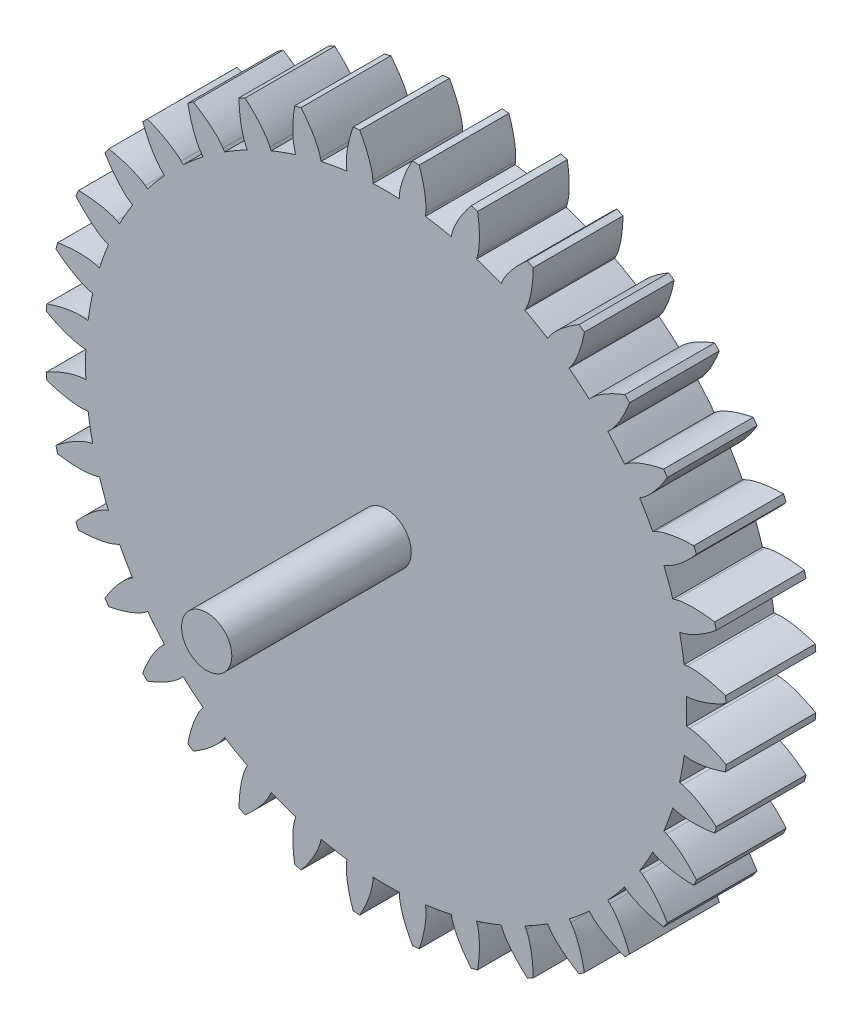
SolidWorks part; units mm, degrees
ref_plane "前视基准面" through (0, 0, 0) normal (0, 0, 1) x (1, 0, 0)
ref_plane "上视基准面" through (0, 0, 0) normal (0, 1, 0) x (1, 0, 0)
ref_plane "右视基准面" through (0, 0, 0) normal (1, 0, 0) x (0, 0, -1)
other "Configuration Table"
sketch "草图1" plane through (0, 0, 0) normal (0, 0, 1) x (1, 0, 0)
  line L0 (0, 0) -> (3, 0) construction
  line L1 (0, 0) -> (2.8978, 0.7765) construction
  line L2 (0, 0) -> (2.7305, 0.701)
  line L3 (2.8978, 0.7765) -> (2.8978, -0.7765) construction
  line L4 (0, 0) -> (2.7305, -0.701)
  circle A0 centre (0, 0) radius 4
  circle A1 centre (0, 0) radius 3 construction
  circle A2 centre (0, 0) radius 1.75
  circle A3 centre (0, 0) radius 2.8191 construction
  circle A4 centre (0, 0) radius 1.4
  spline S0 degree 4 poles (2.7305, 0.701) (2.7514, 0.7063) (2.8083, 0.7255) (2.9105, 0.779) (3.0627, 0.8875) (3.236, 1.0573) (3.4253, 1.3046) (3.6012, 1.6247) (3.742, 2.0003) (3.8364, 2.4221) (3.8779, 2.852) (3.8707, 3.2837) (3.8157, 3.7334) (3.69, 4.2802) (3.4574, 4.9086) (3.0836, 5.5918) (2.5556, 6.2772) (1.9356, 6.8796) (1.2391, 7.3923) (0.4849, 7.8122) (-0.3175, 8.1368) (-1.1468, 8.3674) (-2.0054, 8.5023) (-2.7502, 8.5427) (-3.4127, 8.5171) (-3.8849, 8.4708) (-4.3024, 8.4076) (-4.5772, 8.3558) (-4.9624, 8.2714) (-5.2496, 8.1908) (-5.5362, 8.1071) (-5.6783, 8.056) (-5.7704, 8.0254) knots 0 0 0 0 0 0.005604 0.015718 0.02996 0.048734 0.068727 0.096889 0.125051 0.153212 0.181374 0.209535 0.237696 0.271429 0.327752 0.384075 0.440398 0.496721 0.553044 0.609367 0.66569 0.722013 0.778336 0.834659 0.86282 0.890982 0.909091 0.931818 0.954545 0.977273 1 1 1 1 1 construction
  spline S1 degree 4 poles (2.7305, 0.701) (2.7514, 0.7063) (2.8083, 0.7255) (2.9105, 0.779) (3.0627, 0.8875) (3.236, 1.0573) (3.4253, 1.3046) (3.6012, 1.6247) (3.742, 2.0003) (3.8364, 2.4221) (3.8779, 2.852) (3.8707, 3.2837) (3.8157, 3.7334) (3.69, 4.2802) (3.4574, 4.9086) (3.0836, 5.5918) (2.5556, 6.2772) (1.9356, 6.8796) (1.2391, 7.3923) (0.4849, 7.8122) (-0.3175, 8.1368) (-1.1468, 8.3674) (-2.0054, 8.5023) (-2.7502, 8.5427) (-3.4127, 8.5171) (-3.8849, 8.4708) (-4.2047, 8.4224) (-4.3632, 8.395) (-4.4251, 8.3835) knots 0 0 0 0 0 0.005604 0.015718 0.02996 0.048734 0.068727 0.096889 0.125051 0.153212 0.181374 0.209535 0.237696 0.271429 0.327752 0.384075 0.440398 0.496721 0.553044 0.609367 0.66569 0.722013 0.778336 0.834659 0.86282 0.890982 0.909091 0.909091 0.909091 0.909091 0.909091
  spline S2 degree 4 poles (2.7305, -0.701) (2.7514, -0.7063) (2.8083, -0.7255) (2.9105, -0.779) (3.0627, -0.8875) (3.236, -1.0573) (3.4253, -1.3046) (3.6012, -1.6247) (3.742, -2.0003) (3.8364, -2.4221) (3.8779, -2.852) (3.8707, -3.2837) (3.8157, -3.7334) (3.69, -4.2802) (3.4574, -4.9086) (3.0836, -5.5918) (2.5556, -6.2772) (1.9356, -6.8796) (1.2391, -7.3923) (0.4849, -7.8122) (-0.3175, -8.1368) (-1.1468, -8.3674) (-2.0054, -8.5023) (-2.7502, -8.5427) (-3.4127, -8.5171) (-3.8849, -8.4708) (-4.3024, -8.4076) (-4.5772, -8.3558) (-4.9624, -8.2714) (-5.2496, -8.1908) (-5.5362, -8.1071) (-5.6783, -8.056) (-5.7704, -8.0254) knots 0 0 0 0 0 0.005604 0.015718 0.02996 0.048734 0.068727 0.096889 0.125051 0.153212 0.181374 0.209535 0.237696 0.271429 0.327752 0.384075 0.440398 0.496721 0.553044 0.609367 0.66569 0.722013 0.778336 0.834659 0.86282 0.890982 0.909091 0.931818 0.954545 0.977273 1 1 1 1 1 construction
  spline S3 degree 4 poles (2.7305, -0.701) (2.7514, -0.7063) (2.8083, -0.7255) (2.9105, -0.779) (3.0627, -0.8875) (3.236, -1.0573) (3.4253, -1.3046) (3.6012, -1.6247) (3.742, -2.0003) (3.8364, -2.4221) (3.8779, -2.852) (3.8707, -3.2837) (3.8157, -3.7334) (3.69, -4.2802) (3.4574, -4.9086) (3.0836, -5.5918) (2.5556, -6.2772) (1.9356, -6.8796) (1.2391, -7.3923) (0.4849, -7.8122) (-0.3175, -8.1368) (-1.1468, -8.3674) (-2.0054, -8.5023) (-2.7502, -8.5427) (-3.4127, -8.5171) (-3.8849, -8.4708) (-4.2047, -8.4224) (-4.3632, -8.395) (-4.4251, -8.3835) knots 0 0 0 0 0 0.005604 0.015718 0.02996 0.048734 0.068727 0.096889 0.125051 0.153212 0.181374 0.209535 0.237696 0.271429 0.327752 0.384075 0.440398 0.496721 0.553044 0.609367 0.66569 0.722013 0.778336 0.834659 0.86282 0.890982 0.909091 0.909091 0.909091 0.909091 0.909091
  point P15 (2.8978, 0)
  dimension "齿顶圆直径" = 8
  dimension "分度圆直径" = 6
  dimension "齿根圆直径" = 3.5
  dimension "基圆直径" = 5.6382
  dimension "内孔直径" = 2.8
  dimension "渐近线镜像线夹角" = 15
extrude "凸台-拉伸1" add sketch "草图1" along normal blind 5 contours A0 | A4
extrude "切除-拉伸1" cut sketch "草图1<3>" along normal through all contours A2 S3 A0 S1 region at (3.0753, 0, 0)
sketch "草图1<3>" plane through (0, 0, 0) normal (0, 0, 1) x (1, 0, 0) same geometry as "草图1"
pattern_circular "阵列(圆周)1" count 6 every 60 about axis through (0, 0, 5) along (0, 0, 1) of "切除-拉伸1"
sketch "草图2" plane through (0, 0, 5) normal (0, 0, 1) x (1, 0, 0)
  line L0 (0, 0) -> (18, 0) construction
  line L1 (0, 0) -> (16.8984, 0.7378)
  line L2 (0, 0) -> (16.8984, -0.7378)
  line L3 (16.8984, 0.7378) -> (16.8984, -0.7378) construction
  circle A0 centre (0, 0) radius 18 construction
  circle A1 centre (0, 0) radius 16.9145 construction
  circle A2 centre (0, 0) radius 16.75
  circle A3 centre (0, 0) radius 19
  circle A4 centre (0, 0) radius 1.4
  spline S0 degree 4 poles (16.8984, -0.7378) (16.9305, -0.7392) (16.9946, -0.744) (17.1222, -0.7613) (17.3623, -0.8094) (17.6792, -0.8979) (18.2656, -1.1114) (19.1537, -1.5549) (20.2605, -2.3067) (21.6402, -3.5683) (23.0181, -5.2717) (24.2472, -7.341) (25.2511, -9.7319) (25.9514, -12.2271) (26.3654, -14.7846) (26.5168, -17.4986) (26.353, -20.8608) (25.6449, -24.8182) (24.1592, -29.2488) (21.7683, -33.856) (18.7413, -38.0696) (15.6205, -41.3641) (12.6641, -43.8837) (10.0391, -45.7726) (7.8519, -47.1548) (5.0217, -48.719) (2.0772, -50.063) (-0.9572, -51.1847) (-4.6856, -52.2642) (-7.5306, -52.8747) (-10.0928, -53.2637) (-12.1778, -53.4743) (-13.1552, -53.5512) (-14.0988, -53.6122) (-15.0049, -53.6515) (-15.8075, -53.6779) (-16.967, -53.687) (-17.5735, -53.6824) (-18.4532, -53.6655) (-19.1605, -53.6386) (-19.9868, -53.6008) (-20.868, -53.5426) (-21.9266, -53.4557) (-22.9527, -53.3491) (-23.9974, -53.2227) (-24.7654, -53.1134) (-25.2852, -53.034) (-25.541, -52.9927) knots 0 0 0 0 0 0.001401 0.002802 0.005604 0.010661 0.015718 0.02996 0.048734 0.068727 0.096889 0.125051 0.153212 0.181374 0.209535 0.237696 0.271429 0.327752 0.384075 0.440398 0.496721 0.553044 0.581206 0.609367 0.637529 0.66569 0.722013 0.750174 0.778336 0.834659 0.84874 0.86282 0.869861 0.876901 0.890982 0.900036 0.909091 0.920455 0.926136 0.931818 0.943182 0.954545 0.965909 0.977273 0.988636 1 1 1 1 1 construction
  spline S1 degree 4 poles (16.8984, -0.7378) (16.9305, -0.7392) (16.9946, -0.744) (17.1222, -0.7613) (17.3623, -0.8094) (17.6792, -0.8979) (18.2656, -1.1114) (19.1537, -1.5549) (20.2605, -2.3067) (21.6402, -3.5683) (23.0181, -5.2717) (24.2472, -7.341) (25.2511, -9.7319) (25.9514, -12.2271) (26.3654, -14.7846) (26.5168, -17.4986) (26.353, -20.8608) (25.6449, -24.8182) (24.1592, -29.2488) (21.7683, -33.856) (18.7413, -38.0696) (15.6205, -41.3641) (12.6641, -43.8837) (10.0391, -45.7726) (7.8519, -47.1548) (5.0217, -48.719) (2.0772, -50.063) (-0.9572, -51.1847) (-4.6856, -52.2642) (-7.5306, -52.8747) (-10.0928, -53.2637) (-12.1778, -53.4743) (-13.1552, -53.5512) (-14.0988, -53.6122) (-15.0049, -53.6515) (-15.8075, -53.6779) (-16.6645, -53.6846) (-17.0423, -53.6846) (-17.2312, -53.6835) knots 0 0 0 0 0 0.001401 0.002802 0.005604 0.010661 0.015718 0.02996 0.048734 0.068727 0.096889 0.125051 0.153212 0.181374 0.209535 0.237696 0.271429 0.327752 0.384075 0.440398 0.496721 0.553044 0.581206 0.609367 0.637529 0.66569 0.722013 0.750174 0.778336 0.834659 0.84874 0.86282 0.869861 0.876901 0.890982 0.900036 0.909091 0.909091 0.909091 0.909091 0.909091
  spline S2 degree 4 poles (16.8984, 0.7378) (16.9305, 0.7392) (16.9946, 0.744) (17.1222, 0.7613) (17.3623, 0.8094) (17.6792, 0.8979) (18.2656, 1.1114) (19.1537, 1.5549) (20.2605, 2.3067) (21.6402, 3.5683) (23.0181, 5.2717) (24.2472, 7.341) (25.2511, 9.7319) (25.9514, 12.2271) (26.3654, 14.7846) (26.5168, 17.4986) (26.353, 20.8608) (25.6449, 24.8182) (24.1592, 29.2488) (21.7683, 33.856) (18.7413, 38.0696) (15.6205, 41.3641) (12.6641, 43.8837) (10.0391, 45.7726) (7.8519, 47.1548) (5.0217, 48.719) (2.0772, 50.063) (-0.9572, 51.1847) (-4.6856, 52.2642) (-7.5306, 52.8747) (-10.0928, 53.2637) (-12.1778, 53.4743) (-13.1552, 53.5512) (-14.0988, 53.6122) (-15.0049, 53.6515) (-15.8075, 53.6779) (-16.967, 53.687) (-17.5735, 53.6824) (-18.4532, 53.6655) (-19.1605, 53.6386) (-19.9868, 53.6008) (-20.868, 53.5426) (-21.9266, 53.4557) (-22.9527, 53.3491) (-23.9974, 53.2227) (-24.7654, 53.1134) (-25.2852, 53.034) (-25.541, 52.9927) knots 0 0 0 0 0 0.001401 0.002802 0.005604 0.010661 0.015718 0.02996 0.048734 0.068727 0.096889 0.125051 0.153212 0.181374 0.209535 0.237696 0.271429 0.327752 0.384075 0.440398 0.496721 0.553044 0.581206 0.609367 0.637529 0.66569 0.722013 0.750174 0.778336 0.834659 0.84874 0.86282 0.869861 0.876901 0.890982 0.900036 0.909091 0.920455 0.926136 0.931818 0.943182 0.954545 0.965909 0.977273 0.988636 1 1 1 1 1 construction
  spline S3 degree 4 poles (16.8984, 0.7378) (16.9305, 0.7392) (16.9946, 0.744) (17.1222, 0.7613) (17.3623, 0.8094) (17.6792, 0.8979) (18.2656, 1.1114) (19.1537, 1.5549) (20.2605, 2.3067) (21.6402, 3.5683) (23.0181, 5.2717) (24.2472, 7.341) (25.2511, 9.7319) (25.9514, 12.2271) (26.3654, 14.7846) (26.5168, 17.4986) (26.353, 20.8608) (25.6449, 24.8182) (24.1592, 29.2488) (21.7683, 33.856) (18.7413, 38.0696) (15.6205, 41.3641) (12.6641, 43.8837) (10.0391, 45.7726) (7.8519, 47.1548) (5.0217, 48.719) (2.0772, 50.063) (-0.9572, 51.1847) (-4.6856, 52.2642) (-7.5306, 52.8747) (-10.0928, 53.2637) (-12.1778, 53.4743) (-13.1552, 53.5512) (-14.0988, 53.6122) (-15.0049, 53.6515) (-15.8075, 53.6779) (-16.6645, 53.6846) (-17.0423, 53.6846) (-17.2312, 53.6835) knots 0 0 0 0 0 0.001401 0.002802 0.005604 0.010661 0.015718 0.02996 0.048734 0.068727 0.096889 0.125051 0.153212 0.181374 0.209535 0.237696 0.271429 0.327752 0.384075 0.440398 0.496721 0.553044 0.581206 0.609367 0.637529 0.66569 0.722013 0.750174 0.778336 0.834659 0.84874 0.86282 0.869861 0.876901 0.890982 0.900036 0.909091 0.909091 0.909091 0.909091 0.909091
  point P16 (16.8984, 0)
  dimension "内孔直径" = 2.8
  dimension "分度圆直径" = 36
  dimension "齿顶圆直径" = 38
  dimension "基圆直径" = 33.8289
  dimension "齿根圆直径" = 33.5
  dimension "渐开线镜像线夹角" = 2.5
extrude "凸台-拉伸2" add sketch "草图2" along normal blind 5 contours A3 | A4
extrude "切除-拉伸3" cut sketch "草图2<3>" along normal through all contours S3 L1 A2 L2 S1 A3 region at (18.0071, 0, 5)
sketch "草图2<3>" plane through (0, 0, 5) normal (0, 0, 1) x (1, 0, 0) same geometry as "草图2"
pattern_circular "阵列(圆周)2" count 36 over 360 about axis through (0, 0, 10) along (0, 0, 1) of "切除-拉伸3"
sketch "草图3" plane through (0, 0, 10) normal (0, 0, 1) x (1, 0, 0)
  circle A0 centre (0, 0) radius 1.4
  circle A1 centre (0, 0) radius 1.4 construction
extrude "凸台-拉伸3" add sketch "草图3" along normal blind 10 separate body
extrude "凸台-拉伸4" add sketch "草图3<2>" against normal blind 15
sketch "草图3<2>" plane through (0, 0, 10) normal (0, 0, 1) x (1, 0, 0) same geometry as "草图3"
equation "\"m\"= 1'模数"
equation "\"z\"= 6'齿数"
equation "\"a\"= 20度'压力角"
equation "\"d\"= \"m\" * \"z\"'分度圆直径"
equation "\"da\"= ( \"z\" + 2 ) * \"m\"'齿顶圆直径"
equation "\"df\"= ( \"z\" - 2.5 ) * \"m\"'齿根圆直径"
equation "\"s\"= 0.5 * PI * \"m\"'分度圆齿厚"
equation "\"r\"= 0.38 * \"m\"'齿根圆角"
equation "\"B\"= 0.3 * \"d\"'齿厚"
equation "\"db\"= \"m\" * \"z\" * cos ( \"a\" )'基圆直径"
equation "\"rb\"= \"db\" / 2'基圆半径"
equation "\"齿顶圆直径@草图1\"= \"da\""
equation "\"分度圆直径@草图1\"= \"d\""
equation "\"齿根圆直径@草图1\"= \"df\""
equation "\"基圆直径@草图1\"= \"db\""
equation "\"渐近线镜像线夹角@草图1\"= 360 / 4 / \"z\""
equation "\"h\"= 5'齿轮厚度"
equation "\"ir\"= 2.8'内孔直径"
equation "\"内孔直径@草图1\"= \"ir\""
equation "\"齿轮厚@凸台-拉伸1\"= \"h\""
equation "\"齿轮夹角@阵列(圆周)1\"= 360 / \"z\""
equation "\"齿数@阵列(圆周)1\"= \"z\""
equation "\"m1\"= 1'模数"
equation "\"z1\"= 36'齿数"
equation "\"a1\"= 20度'压力角"
equation "\"d1\"= \"m1\" * \"z1\"'分度圆直径"
equation "\"da1\"= ( \"z1\" + 2 ) * \"m1\"'齿顶圆直径"
equation "\"df1\"= ( \"z1\" - 2.5 ) * \"m1\"'齿根圆直径"
equation "\"s1\"= 0.5 * PI * \"m1\"'分度圆齿厚"
equation "\"r1\"= 0.38 * \"m1\"'齿根圆角"
equation "\"B1\"= 0.3 * \"d1\"'齿厚"
equation "\"db1\"= \"m1\" * \"z1\" * cos ( \"a1\" )'基圆直径"
equation "\"rb1\"= \"db1\" / 2'基圆半径"
equation "\"分度圆直径@草图2\"= \"d1\""
equation "\"齿顶圆直径@草图2\"= \"da1\""
equation "\"基圆直径@草图2\"= \"db1\""
equation "\"齿根圆直径@草图2\"= \"df1\""
equation "\"渐开线镜像线夹角@草图2\"= 360 / 4 / \"z1\""
equation "\"内孔直径@草图2\"= \"ir\""
equation "\"二层齿轮厚@凸台-拉伸2\" = \"h1\""
equation "\"h1\"= 5'齿轮厚度"
equation "\"二层齿数@阵列(圆周)2\"= \"z1\""
